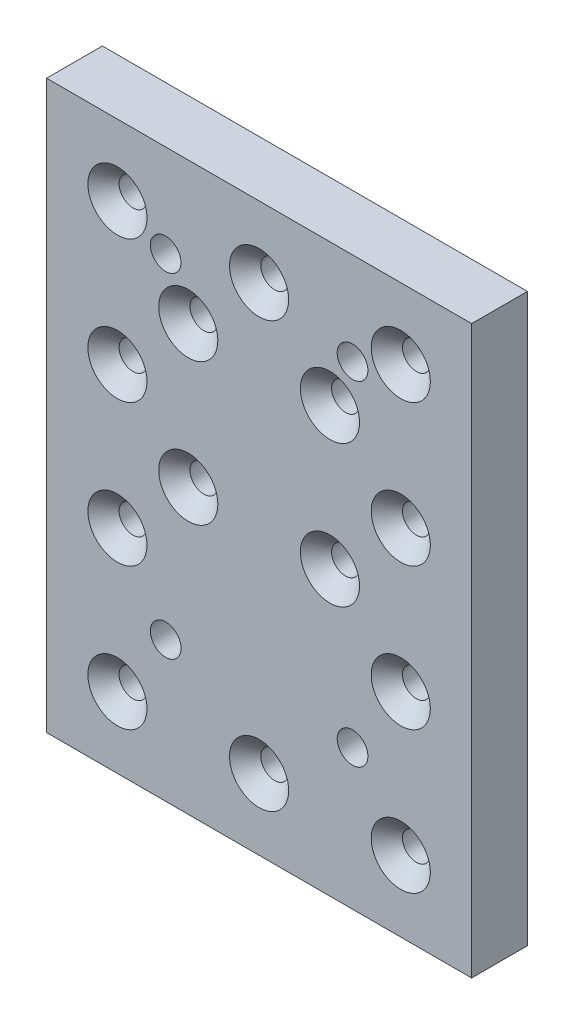
SolidWorks part; units mm, degrees
ref_plane "Front Plane" through (0, 0, 0) normal (0, 0, 1) x (1, 0, 0)
ref_plane "Top Plane" through (0, 0, 0) normal (0, 1, 0) x (1, 0, 0)
ref_plane "Right Plane" through (0, 0, 0) normal (1, 0, 0) x (0, 0, -1)
sketch "Sketch1" plane through (0, 0, 0) normal (0, 0, 1) x (1, 0, 0)
  line L9 (-64.52, -20.9042) -> (11.68, -20.9042)
  line L10 (11.68, -20.9042) -> (11.68, 80.6958)
  line L11 (11.68, 80.6958) -> (-64.52, 80.6958)
  line L12 (-64.52, 80.6958) -> (-64.52, -20.9042)
  circle A0 centre (-1.02, 17.1958) radius 2.5
  circle A1 centre (-13.72, 29.8958) radius 2.5
  circle A3 centre (-1.02, 42.5958) radius 2.5
  circle A5 centre (-13.72, 55.2958) radius 2.5
  circle A7 centre (-1.02, 67.9958) radius 2.5
  circle A10 centre (-1.02, 17.1958) radius 3.429 construction
  circle A12 centre (-13.72, 29.8958) radius 3.429 construction
  circle A14 centre (-1.02, 42.5958) radius 3.429 construction
  circle A16 centre (-13.72, 55.2958) radius 3.429 construction
  circle A18 centre (-1.02, 67.9958) radius 3.429 construction
  circle A20 centre (-26.42, 67.9958) radius 3.429 construction
  circle A22 centre (-39.12, 55.2958) radius 3.429 construction
  circle A24 centre (-51.82, 67.9958) radius 3.429 construction
  circle A26 centre (-51.82, 42.5958) radius 3.429 construction
  circle A28 centre (-51.82, 17.1958) radius 3.429 construction
  circle A30 centre (-39.12, 29.8958) radius 3.429 construction
  circle A32 centre (-39.12, 4.4958) radius 3.429 construction
  circle A34 centre (-13.72, 4.4958) radius 3.429 construction
  circle A36 centre (-1.02, -8.2042) radius 3.429 construction
  circle A38 centre (-26.42, -8.2042) radius 3.429 construction
  circle A40 centre (-51.82, -8.2042) radius 3.429 construction
  circle A41 centre (-26.42, 67.9958) radius 2.5
  circle A42 centre (-39.12, 55.2958) radius 2.5
  circle A43 centre (-51.82, 67.9958) radius 2.5
  circle A44 centre (-51.82, 42.5958) radius 2.5
  circle A45 centre (-51.82, 17.1958) radius 2.5
  circle A46 centre (-39.12, 29.8958) radius 2.5
  circle A47 centre (-39.12, 4.4958) radius 2.5 construction
  circle A48 centre (-13.72, 4.4958) radius 2.5 construction
  circle A49 centre (-1.02, -8.2042) radius 2.5
  circle A50 centre (-26.42, -8.2042) radius 2.5
  circle A51 centre (-51.82, -8.2042) radius 2.5
  circle A56 centre (-43.17, 4.2072) radius 2.75
  circle A57 centre (-9.67, 4.2072) radius 2.75
  circle A58 centre (-9.67, 64.1072) radius 2.75
  circle A59 centre (-43.17, 64.1072) radius 2.75
  point P94 (-72.4046, 61.4683)
  dimension "D21" = 5
extrude "Boss-Extrude1" add sketch "Sketch1" along normal blind 10
chamfer "Chamfer1" distance 2.8 angle 45 14 edges at (1.48, 67.9958, 10) (-23.92, 67.9958, 10) (-49.32, 17.1958, 10) (-49.32, 42.5958, 10) (-49.32, 67.9958, 10) (-11.22, 55.2958, 10) (-36.62, 55.2958, 10) (-36.62, 29.8958, 10) (-11.22, 29.8958, 10) (1.48, 42.5958, 10) (1.48, 17.1958, 10) (1.48, -8.2042, 10) (-23.92, -8.2042, 10) (-49.32, -8.2042, 10)
